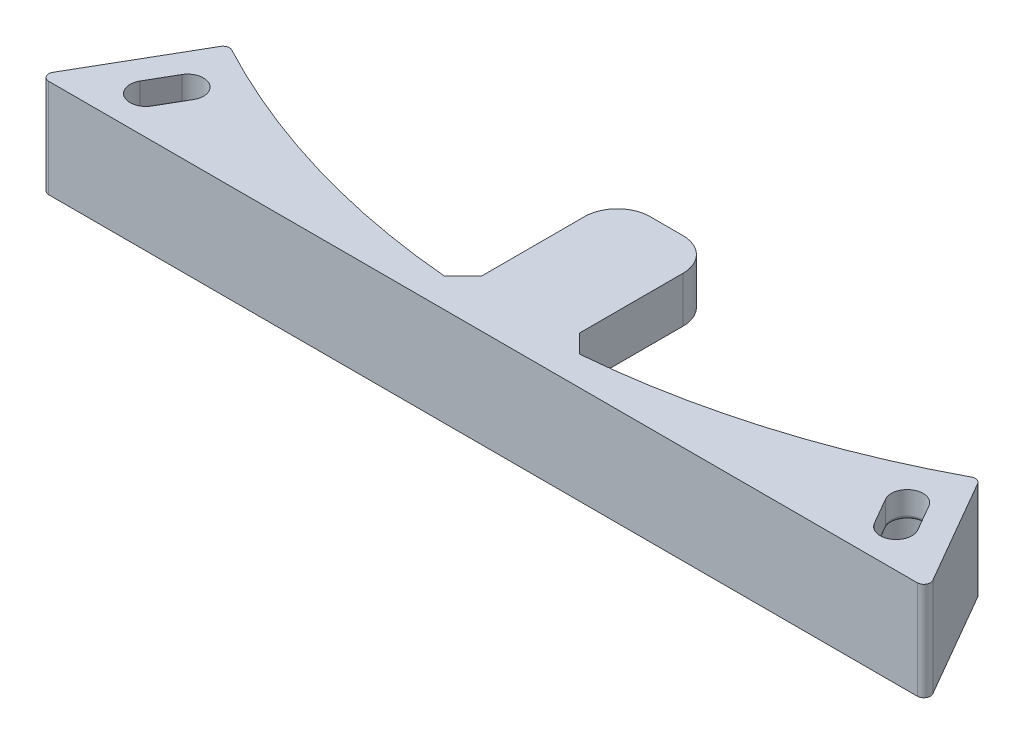
SolidWorks part; units mm, degrees
ref_plane "Front Plane" through (0, 0, 0) normal (0, 0, 1) x (1, 0, 0)
ref_plane "Top Plane" through (0, 0, 0) normal (0, 1, 0) x (1, 0, 0)
ref_plane "Right Plane" through (0, 0, 0) normal (1, 0, 0) x (0, 0, -1)
sketch "Sketch1" plane through (0, 0, 0) normal (0, 1, 0) x (1, 0, 0)
  line L0 (-57.2863, -105.4433) -> (-68, -124)
  line L1 (-68, -124) -> (68, -124)
  line L2 (68, -124) -> (57.2863, -105.4433)
  arc A1 (-57.2863, -105.4433) -> (57.2863, -105.4433) centre (0, 0) ccw
  point P5 (99.8827, -66.3233)
  point P8 (0, 0)
  point P9 (-94.9361, -73.3971)
  point P10 (-126.254, -124)
  point P11 (-83.9524, -85.7438)
  point P12 (-102.9115, -124)
  dimension "D1" = 120
  dimension "D2" = 4
  dimension "D3" = 60
  dimension "D4" = 136
extrude "Boss-Extrude1" add sketch "Sketch1" along normal blind 15
sketch "Sketch2" plane through (0, 15, 0) normal (0, 1, 0) x (1, 0, 0)
  line L0 (-54.9043, -114.1675) -> (-57.2293, -118.1945) construction
  line L1 (-52.8042, -115.38) -> (-55.1292, -119.407)
  line L2 (-57.0044, -112.955) -> (-59.3294, -116.982)
  line L3 (-57.2863, -105.4433) -> (-68, -124) construction
  line L4 (0, -124) -> (0, -120) construction
  line L5 (-68, -124) -> (68, -124) construction
  line L6 (-54.9043, -114.1675) -> (-51.5525, -108.3621) construction
  line L7 (-57.2293, -118.1945) -> (-60.581, -124) construction
  line L8 (54.9043, -114.1675) -> (57.2293, -118.1945) construction
  line L9 (52.8042, -115.38) -> (55.1292, -119.407)
  line L10 (57.0044, -112.955) -> (59.3294, -116.982)
  arc A0 (-52.8042, -115.38) -> (-57.0044, -112.955) centre (-54.9043, -114.1675) ccw
  arc A1 (-59.3294, -116.982) -> (-55.1292, -119.407) centre (-57.2293, -118.1945) ccw
  arc A2 (-57.2863, -105.4433) -> (57.2863, -105.4433) centre (0, 0) ccw construction
  arc A3 (52.8042, -115.38) -> (57.0044, -112.955) centre (54.9043, -114.1675) cw
  arc A4 (59.3294, -116.982) -> (55.1292, -119.407) centre (57.2293, -118.1945) cw
  point P2 (-56.0668, -116.181)
  point P20 (-54.2656, -113.0614)
  point P23 (56.0668, -116.181)
  point P28 (-57.779, -119.1466)
  dimension "D3" = 9.5
  dimension "D1" = 4.85
  dimension "D2" = 4
extrude "Cut-Extrude1" cut sketch "Sketch2" against normal through all
sketch "Sketch3" plane through (0, 15, 0) normal (0, 1, 0) x (1, 0, 0)
  line L0 (-54.9168, -114.1892) -> (-57.2168, -118.1729) construction
  line L1 (-51.0197, -116.4392) -> (-53.3197, -120.4229)
  line L2 (-58.8139, -111.9392) -> (-61.1139, -115.9229)
  line L3 (-58.1669, -114.9685) -> (-53.9667, -117.3935) construction
  line L4 (-57.2863, -105.4433) -> (-68, -124) construction
  line L5 (0, -120) -> (0, -124) construction
  line L6 (-68, -124) -> (68, -124) construction
  line L7 (-52.1697, -118.431) -> (-53.9667, -117.3935) construction
  line L8 (-55.1292, -119.407) -> (-52.8042, -115.38) construction
  line L9 (-59.9639, -113.931) -> (-58.1669, -114.9685) construction
  line L10 (-57.0044, -112.955) -> (-59.3294, -116.982) construction
  line L11 (54.9168, -114.1892) -> (57.2168, -118.1729) construction
  line L12 (51.0197, -116.4392) -> (53.3197, -120.4229)
  line L13 (58.8139, -111.9392) -> (61.1139, -115.9229)
  arc A0 (-51.0197, -116.4392) -> (-58.8139, -111.9392) centre (-54.9168, -114.1892) ccw
  arc A1 (-61.1139, -115.9229) -> (-53.3197, -120.4229) centre (-57.2168, -118.1729) ccw
  arc A2 (-57.2863, -105.4433) -> (57.2863, -105.4433) centre (0, 0) ccw construction
  arc A4 (51.0197, -116.4392) -> (58.8139, -111.9392) centre (54.9168, -114.1892) cw
  arc A5 (61.1139, -115.9229) -> (53.3197, -120.4229) centre (57.2168, -118.1729) cw
  point P2 (-56.0668, -116.181)
  point P26 (56.0668, -116.181)
  dimension "D2" = 13.6
  dimension "D1" = 9
extrude "Cut-Extrude3" cut sketch "Sketch3" against normal through all from offset 4 offset against normal yes
fillet "Fillet1" radius 1 4 edges at (-68, 7.5, 124) (-57.2863, 7.5, 105.4433) (68, 7.5, 124) (57.2863, 7.5, 105.4433)
fillet "Fillet2" radius 0.5 16 edges at (58.4418, 11, 120.2947) (53.9667, 11, 117.3935) (53.6918, 11, 112.0674) (-53.6918, 11, 112.0674) (-58.1669, 11, 114.9685) (-58.4418, 11, 120.2947) (-52.1697, 11, 118.431) (-59.4668, 11, 122.07) (-59.9639, 11, 113.931) (59.4668, 11, 122.07) (52.1697, 11, 118.431) (52.6668, 11, 110.2921) (58.1669, 11, 114.9685) (-53.9667, 11, 117.3935) (-52.6668, 11, 110.2921) (59.9639, 11, 113.931)
sketch "Sketch4" plane through (0, 15, 0) normal (0, 1, 0) x (1, 0, 0)
  line L0 (0, -124) -> (0, -96) construction
  line L1 (-66.2679, -124) -> (66.2679, -124) construction
  line L2 (-7.5, -124) -> (-7.5, -96)
  line L3 (7.5, -124) -> (7.5, -96)
  line L4 (-7.5, -96) -> (7.5, -96)
  line L5 (-7.5, -124) -> (7.5, -124)
  dimension "D1" = 15
  dimension "D2" = 28
extrude "Boss-Extrude2" add sketch "Sketch4" against normal blind 7
chamfer "Chamfer1" distance 3 angle 45 2 edges at (-7.5, 11.5, 119.7654) (7.5, 11.5, 119.7654) first distance on face at (-7.5, 11.5, 107.8827) first distance on face at (7.5, 11.5, 107.8827)
fillet "Fillet3" radius 5 2 edges at (-7.5, 11.5, 96) (7.5, 11.5, 96)
